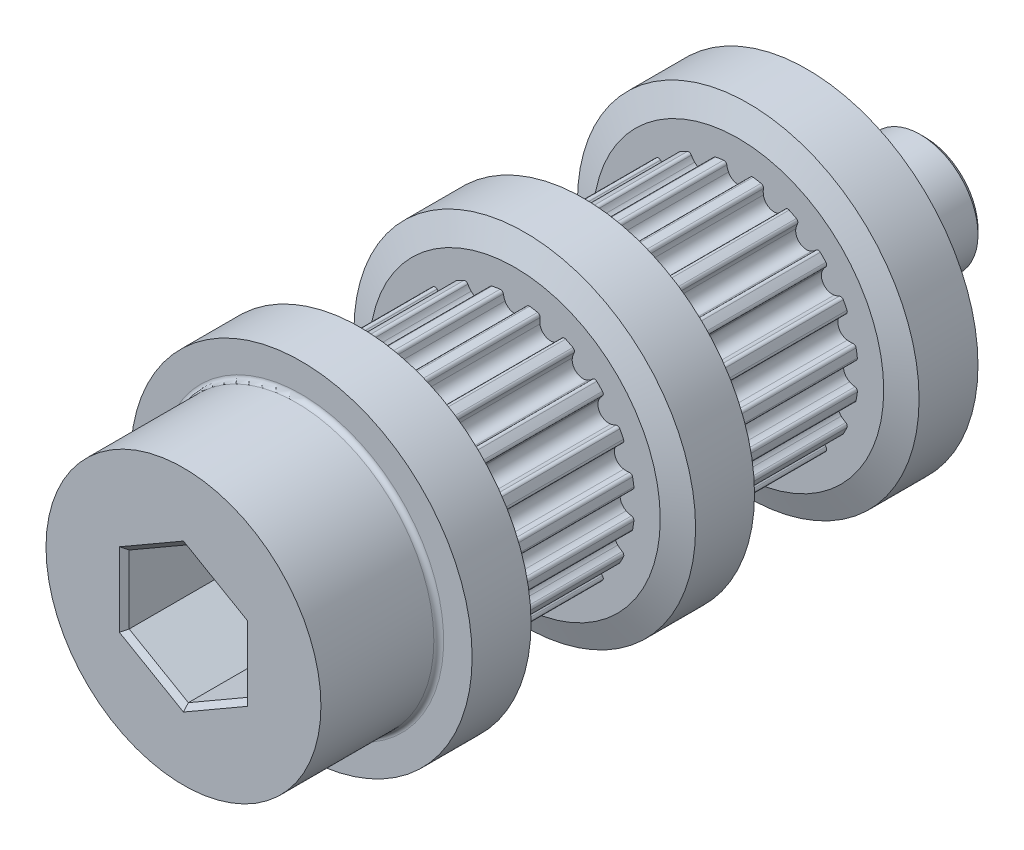
SolidWorks part; units mm, degrees
ref_plane "Front Plane" through (0, 0, 0) normal (0, 0, 1) x (1, 0, 0)
ref_plane "Top Plane" through (0, 0, 0) normal (0, 1, 0) x (1, 0, 0)
ref_plane "Right Plane" through (0, 0, 0) normal (1, 0, 0) x (0, 0, -1)
sketch "Sketch1" plane through (0, 0, 0) normal (0, 0, 1) x (1, 0, 0)
  point P0 (-2.841, 8.6995)
  line B0 (-1.7499, 5.3585) -> (1.7499, 5.3585) construction
  line B1 (0, 0) -> (0, 5.3585) construction
  line B2 (0, 5.3585) -> (0, 11.2111) construction
  line B3 (0, 6.3625) -> (1.9751, 6.0482) construction
  line B4 (1.9751, 6.0482) -> (2.6648, 5.8229) construction
  line B5 (1.9751, 6.0482) -> (1.7499, 5.3585) construction
  line B6 (-1.9751, 6.0482) -> (-1.7499, 5.3585) construction
  line B7 (-1.8963, 5.8067) -> (-2.841, 8.6995)
  line B8 (-2.841, 8.6995) -> (2.841, 8.6995)
  line B9 (2.841, 8.6995) -> (1.8963, 5.8067)
  circle B10 centre (0, 0) radius 6.3625 construction
  circle B11 centre (0, 0) radius 8.6995 construction
  circle B12 centre (0, 0) radius 6.1085 construction
  arc B13 (-0.4989, 5.6703) -> (0.4989, 5.6703) centre (0, 5.9135) ccw
  arc B14 (-0.4989, 5.6703) -> (-0.5855, 5.9387) centre (0.4, 6.1085) cw
  arc B15 (-1.8963, 5.8067) -> (-0.7518, 6.0621) centre (0, 0) cw
  arc B16 (-0.5855, 5.9387) -> (-0.7518, 6.0621) centre (-0.7333, 5.9132) ccw
  arc B17 (1.8963, 5.8067) -> (0.7518, 6.0621) centre (0, 0) ccw
  arc B18 (0.5855, 5.9387) -> (0.7518, 6.0621) centre (0.7333, 5.9132) cw
  arc B19 (0.4989, 5.6703) -> (0.5855, 5.9387) centre (-0.4, 6.1085) ccw
sketch_block_instance "Block-Gt Timing Belt Pulley Groove-1"
sketch_block "Block-Gt Timing Belt Pulley Groove" parameters "D1"=12.725, "D2"=17.399, "D6"=0.555, "D7"=1, "D9"=0.15, "D3"=9.6972, "D4"=4.8486, "D5"=2, "D8"=0.254, "D10"=0.4, "D11"=0.75
sketch "Sketch9" plane through (0, 0, 0) normal (0, 0, 1) x (1, 0, 0)
  line L1 (0, 3.1927) -> (-2.765, 1.5964) construction
  line L2 (-2.765, 1.5964) -> (-2.765, -1.5964) construction
  line L3 (-2.765, -1.5964) -> (0, -3.1927) construction
  line L4 (0, -3.1927) -> (2.765, -1.5964) construction
  line L5 (2.765, -1.5964) -> (2.765, 1.5964) construction
  line L6 (2.765, 1.5964) -> (0, 3.1927) construction
  circle A0 centre (0, 0) radius 2.765 construction
  dimension "D1" = 5.53
sketch "Sketch2" plane through (0, 0, 0) normal (1, 0, 0) x (0, 0, -1)
  line L0 (-3.685, 6.1085) -> (3.685, 6.1085)
  line L1 (-18.57, 0) -> (7.19, 0) construction
  line L2 (-3.685, 6.1085) -> (-3.685, 7.404)
  line L3 (-3.685, 7.404) -> (-4.19, 8.6995)
  line L4 (-4.19, 8.6995) -> (-7.19, 8.6995)
  line L5 (-7.19, 8.6995) -> (-7.695, 7.404)
  line L6 (3.685, 6.1085) -> (3.685, 7.404)
  line L7 (3.685, 7.404) -> (4.19, 8.6995)
  line L8 (4.19, 8.6995) -> (7.19, 8.6995)
  line L9 (7.19, 8.6995) -> (7.19, 0)
  line L10 (0, 6.1085) -> (0, 0) construction
  line L11 (-18.57, 0) -> (7.19, 0)
  line L12 (-7.695, 7.404) -> (-7.695, 6.1085)
  line L13 (-7.695, 6.1085) -> (-15.065, 6.1085)
  line L14 (-15.065, 6.1085) -> (-15.065, 7.404)
  line L15 (-15.065, 7.404) -> (-15.57, 8.6995)
  line L16 (-15.57, 8.6995) -> (-18.57, 8.6995)
  line L17 (-18.57, 8.6995) -> (-18.57, 0)
  point P19 (-16.5212, 0)
  dimension "D1" = 12.217
  dimension "D2" = 7.37
  dimension "D3" = 8.38
  dimension "D4" = 17.399
  dimension "D5" = 14.808
  dimension "D6" = 3
revolve "Revolve1" add sketch "Sketch2" angle 360 about L11
sketch "Sketch10" plane through (0, 0, 18.57) normal (0, 0, 1) x (1, 0, 0)
  circle A0 centre (0, 0) radius 7
  dimension "D1" = 14
extrude "Boss-Extrude1" add sketch "Sketch10" along normal blind 6
sketch "Sketch13" plane through (0, 0, -7.19) normal (0, 0, -1) x (-1, 0, 0)
  circle A0 centre (0, 0) radius 2.95
  dimension "D1" = 5.9
extrude "Boss-Extrude2" add sketch "Sketch13" along normal blind 6
sketch "Sketch5" plane through (0, 0, 0) normal (0, 0, 1) x (1, 0, 0)
  line L0 (2.841, 8.6995) -> (1.8963, 5.8067) construction
  line L1 (-1.8963, 5.8067) -> (-2.841, 8.6995) construction
  line L2 (-2.841, 8.6995) -> (2.841, 8.6995) construction
  line L3 (2.841, 8.6995) -> (1.8963, 5.8067)
  line L4 (-1.8963, 5.8067) -> (-2.841, 8.6995)
  line L5 (-2.841, 8.6995) -> (2.841, 8.6995)
  arc A0 (1.8963, 5.8067) -> (0.7518, 6.0621) centre (0, 0) ccw construction
  arc A1 (0.7518, 6.0621) -> (0.5855, 5.9387) centre (0.7333, 5.9132) ccw construction
  arc A2 (0.4989, 5.6703) -> (0.5855, 5.9387) centre (-0.4, 6.1085) ccw construction
  arc A3 (-0.4989, 5.6703) -> (0.4989, 5.6703) centre (0, 5.9135) ccw construction
  arc A4 (-0.5855, 5.9387) -> (-0.4989, 5.6703) centre (0.4, 6.1085) ccw construction
  arc A5 (-0.5855, 5.9387) -> (-0.7518, 6.0621) centre (-0.7333, 5.9132) ccw construction
  arc A6 (-0.7518, 6.0621) -> (-1.8963, 5.8067) centre (0, 0) ccw construction
  arc A7 (1.8963, 5.8067) -> (0.7518, 6.0621) centre (0, 0) ccw
  arc A8 (0.7518, 6.0621) -> (0.5855, 5.9387) centre (0.7333, 5.9132) ccw
  arc A9 (0.4989, 5.6703) -> (0.5855, 5.9387) centre (-0.4, 6.1085) ccw
  arc A10 (-0.4989, 5.6703) -> (0.4989, 5.6703) centre (0, 5.9135) ccw
  arc A11 (-0.5855, 5.9387) -> (-0.4989, 5.6703) centre (0.4, 6.1085) ccw
  arc A12 (-0.5855, 5.9387) -> (-0.7518, 6.0621) centre (-0.7333, 5.9132) ccw
  arc A13 (-0.7518, 6.0621) -> (-1.8963, 5.8067) centre (0, 0) ccw
extrude "Cut-Extrude1" cut sketch "Sketch5" against normal up to surface and the other way up to surface up to face at (6.1085, 0, -3.685) other way up to face at (7.404, 0, 3.685)
sketch "Sketch7" plane through (0, 0, 7.695) normal (0, 0, 1) x (1, 0, 0)
  line L3 (1.8963, 5.8067) -> (2.841, 8.6995)
  line L4 (2.841, 8.6995) -> (-2.841, 8.6995)
  line L5 (-2.841, 8.6995) -> (-1.8963, 5.8067)
  line L6 (1.8963, 5.8067) -> (2.841, 8.6995)
  line L7 (2.841, 8.6995) -> (-2.841, 8.6995)
  line L8 (-2.841, 8.6995) -> (-1.8963, 5.8067)
  arc A7 (-0.7518, 6.0621) -> (-1.8963, 5.8067) centre (0, 0) ccw
  arc A8 (-0.5855, 5.9387) -> (-0.7518, 6.0621) centre (-0.7333, 5.9132) ccw
  arc A9 (-0.5855, 5.9387) -> (-0.4989, 5.6703) centre (0.4, 6.1085) ccw
  arc A10 (-0.4989, 5.6703) -> (0.4989, 5.6703) centre (0, 5.9135) ccw
  arc A11 (0.4989, 5.6703) -> (0.5855, 5.9387) centre (-0.4, 6.1085) ccw
  arc A12 (0.7518, 6.0621) -> (0.5855, 5.9387) centre (0.7333, 5.9132) ccw
  arc A13 (1.8963, 5.8067) -> (0.7518, 6.0621) centre (0, 0) ccw
  arc A14 (-0.7518, 6.0621) -> (-1.8963, 5.8067) centre (0, 0) ccw
  arc A15 (-0.5855, 5.9387) -> (-0.7518, 6.0621) centre (-0.7333, 5.9132) ccw
  arc A16 (-0.5855, 5.9387) -> (-0.4989, 5.6703) centre (0.4, 6.1085) ccw
  arc A17 (-0.4989, 5.6703) -> (0.4989, 5.6703) centre (0, 5.9135) ccw
  arc A18 (0.4989, 5.6703) -> (0.5855, 5.9387) centre (-0.4, 6.1085) ccw
  arc A19 (0.7518, 6.0621) -> (0.5855, 5.9387) centre (0.7333, 5.9132) ccw
  arc A20 (1.8963, 5.8067) -> (0.7518, 6.0621) centre (0, 0) ccw
  dimension "D1" = 0
extrude "Cut-Extrude3" cut sketch "Sketch7" along normal up to surface (7.37 mm away) up to face at (7.404, 0, 15.065)
pattern_circular "CirPattern1" count 20 over 360 about axis through (0, 0, 18.57) along (0, 0, 1) of "Cut-Extrude1", "Cut-Extrude3"
sketch "Sketch11" plane through (0, 0, 18.57) normal (0, 0, 1) x (1, 0, 0)
  line L24 (0, 3.4814) -> (-3.015, 1.7407)
  line L25 (-3.015, 1.7407) -> (-3.015, -1.7407)
  line L26 (-3.015, -1.7407) -> (0, -3.4814)
  line L27 (0, -3.4814) -> (3.015, -1.7407)
  line L28 (3.015, -1.7407) -> (3.015, 1.7407)
  line L29 (3.015, 1.7407) -> (0, 3.4814)
  line L30 (0, 3.4814) -> (-3.015, 1.7407)
  line L31 (-3.015, 1.7407) -> (-3.015, -1.7407)
  line L32 (-3.015, -1.7407) -> (0, -3.4814)
  line L33 (0, -3.4814) -> (3.015, -1.7407)
  line L34 (3.015, -1.7407) -> (3.015, 1.7407)
  line L35 (3.015, 1.7407) -> (0, 3.4814)
  dimension "D1" = 0.25
extrude "Cut-Extrude4" cut sketch "Sketch11" along normal through all
fillet "Fillet1" radius 0.25 2 edges at (7, 0, 18.57) (-2.95, 0, -7.19)
chamfer "Chamfer1" distance 0.25 angle 45 7 edges at (-2.95, 0, -13.19) (-3.015, 0, 24.57) (-1.5075, 2.6111, 24.57) (1.5075, 2.6111, 24.57) (3.015, 0, 24.57) (1.5075, -2.6111, 24.57) (-1.5075, -2.6111, 24.57)
